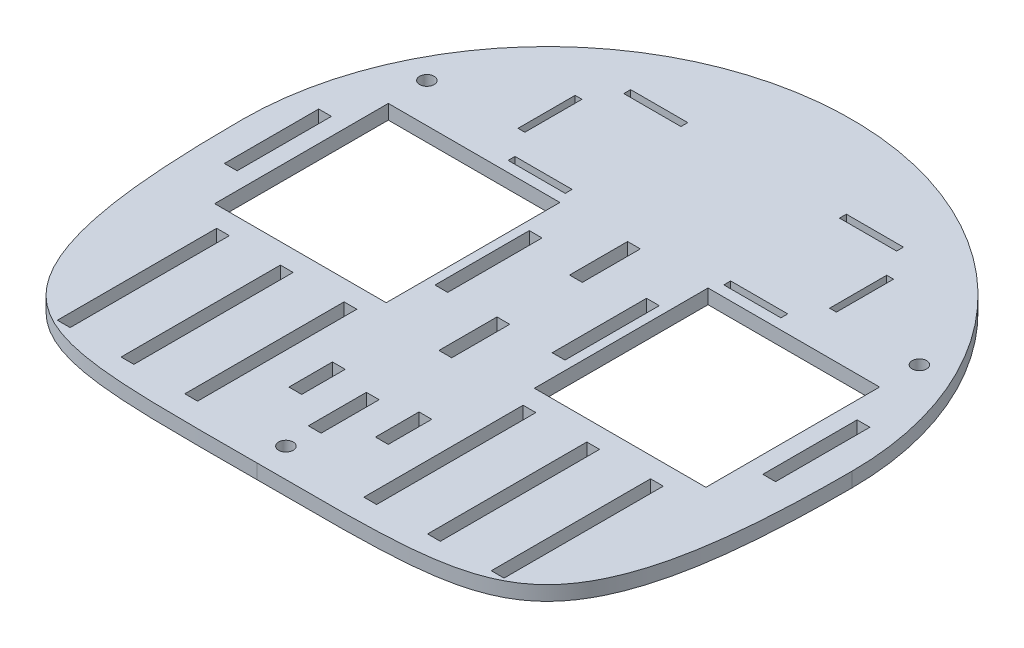
SolidWorks part; units mm, degrees
ref_plane "Front Plane" through (0, 0, 0) normal (0, 0, 1) x (1, 0, 0)
ref_plane "Top Plane" through (0, 0, 0) normal (0, 1, 0) x (1, 0, 0)
ref_plane "Right Plane" through (0, 0, 0) normal (1, 0, 0) x (0, 0, -1)
sketch "Sketch1" plane through (0, 0, 0) normal (0, 1, 0) x (1, 0, 0)
  line L0 (0, 0) -> (-157.9039, -157.9039) construction
  line L1 (0, -127) -> (0, 133.35) construction
  arc A0 (133.35, 0) -> (-133.35, 0) centre (0, 0) ccw
  spline S0 degree 3 poles (-133.35, 0) (-133.35, -51.198) (-123.8034, -129.8051) (-58.428, -127) (0, -127) knots 0 0 0 0 0.502616 1 1 1 1
  spline S1 degree 3 poles (133.35, 0) (133.35, -51.198) (123.8034, -129.8051) (58.428, -127) (0, -127) knots 0 0 0 0 0.502616 1 1 1 1
  dimension "D1" = 266.7
extrude "Base" add sketch "Sketch1" along normal blind 6.35
sketch "ShaftLayout" plane through (0, 6.35, 0) normal (0, 1, 0) x (1, 0, 0)
  line L0 (-133.35, 0) -> (133.35, 0) construction
  line L1 (0, 133.35) -> (0, -127) construction
  line L2 (-113.4353, -6.35) -> (-103.5293, -6.35)
  line L3 (-36.3853, -38) -> (-94.3853, -38)
  line L4 (-36.3853, -38) -> (-36.3853, 38)
  line L5 (-36.3853, 38) -> (-94.3853, 38)
  line L6 (-94.3853, -38) -> (-94.3853, 38)
  line L7 (-36.3853, -38) -> (-94.3853, 38) construction
  line L8 (-36.3853, 38) -> (-94.3853, -38) construction
  line L9 (-100.7353, -15.875) -> (-103.5293, -15.875)
  line L10 (-100.7353, -15.875) -> (-100.7353, 15.875)
  line L11 (-100.7353, 15.875) -> (-103.5293, 15.875)
  line L12 (-103.5293, -15.875) -> (-103.5293, 15.875)
  line L13 (-100.7353, -15.875) -> (-103.5293, 15.875) construction
  line L14 (-100.7353, 15.875) -> (-103.5293, -15.875) construction
  line L15 (-113.4353, -6.35) -> (-113.4353, 6.35)
  line L16 (-103.5293, -6.35) -> (-103.5293, 6.35)
  line L17 (-113.4353, 6.35) -> (-103.5293, 6.35)
  line L18 (-113.4353, -6.35) -> (-103.5293, 6.35) construction
  line L19 (-103.5293, -6.35) -> (-113.4353, 6.35) construction
  line L20 (-115.0228, -9.525) -> (-113.4353, -9.525)
  line L21 (-115.0228, -9.525) -> (-115.0228, 9.525)
  line L22 (-113.4353, -9.525) -> (-113.4353, 9.525)
  line L23 (-115.0228, 9.525) -> (-113.4353, 9.525)
  line L24 (-115.0228, -9.525) -> (-113.4353, 9.525) construction
  line L25 (-113.4353, -9.525) -> (-115.0228, 9.525) construction
  line L26 (-126.1353, -7.9375) -> (-115.0228, -7.9375)
  line L27 (-126.1353, -7.9375) -> (-126.1353, 7.9375)
  line L28 (-115.0228, -7.9375) -> (-115.0228, 7.9375)
  line L29 (-126.1353, 7.9375) -> (-115.0228, 7.9375)
  line L30 (-126.1353, -7.9375) -> (-115.0228, 7.9375) construction
  line L31 (-115.0228, -7.9375) -> (-126.1353, 7.9375) construction
  line L32 (-17.3353, -7.9375) -> (-28.4478, -7.9375)
  line L33 (-30.0353, -9.525) -> (-28.4478, -9.525)
  line L34 (-30.0353, -9.525) -> (-30.0353, 9.525)
  line L35 (-30.0353, 9.525) -> (-28.4478, 9.525)
  line L36 (-28.4478, -9.525) -> (-28.4478, 9.525)
  line L37 (-30.0353, -9.525) -> (-28.4478, 9.525) construction
  line L38 (-30.0353, 9.525) -> (-28.4478, -9.525) construction
  line L39 (-17.3353, -7.9375) -> (-17.3353, 7.9375)
  line L40 (-28.4478, -7.9375) -> (-28.4478, 7.9375)
  line L41 (-17.3353, 7.9375) -> (-28.4478, 7.9375)
  line L42 (-17.3353, -7.9375) -> (-28.4478, 7.9375) construction
  line L43 (-28.4478, -7.9375) -> (-17.3353, 7.9375) construction
  line L45 (-67.3853, -10.033) -> (-56.3853, -10.033)
  line L46 (-67.3853, -10.033) -> (-67.3853, 10.033)
  line L47 (-67.3853, 10.033) -> (-56.3853, 10.033)
  line L48 (-56.3853, -10.033) -> (-56.3853, 10.033)
  line L49 (-67.3853, -10.033) -> (-56.3853, 10.033) construction
  line L50 (-67.3853, 10.033) -> (-56.3853, -10.033) construction
  arc A0 (133.35, 0) -> (-133.35, 0) centre (0, 0) ccw construction
  point P10 (-65.3853, 0)
  point P15 (-102.1323, 0)
  point P20 (-29.2416, 0)
  point P21 (-108.4823, 0)
  point P22 (-114.2291, 0)
  point P23 (-120.5791, 0)
  point P40 (-61.8853, 0)
  point P41 (-22.8916, 0)
  dimension "D1" = 58
  dimension "D2" = 76
  dimension "D3" = 6.35
  dimension "D4" = 2.794
  dimension "D5" = 31.75
  dimension "D6" = 9.906
  dimension "D7" = 12.7
  dimension "D8" = 19.05
  dimension "D9" = 1.5875
  dimension "D10" = 12.7
  dimension "D11" = 15.875
  dimension "D12" = 19.05
  dimension "D13" = 1.5875
  dimension "D14" = 15.875
  dimension "D15" = 12.7
  dimension "D16" = 6.35
  dimension "D17" = 20.066
  dimension "D18" = 20
  dimension "D19" = 11
sketch "MotorLayout" plane through (0, 6.35, 0) normal (0, 1, 0) x (1, 0, 0)
  line L0 (-97.7353, -81.74) -> (-117.7353, -81.74) construction
  line L1 (-97.7353, -110.24) -> (-21.7353, -110.24)
  line L2 (-97.7353, -110.24) -> (-97.7353, -53.24)
  line L3 (-97.7353, -53.24) -> (-21.7353, -53.24)
  line L4 (-21.7353, -110.24) -> (-21.7353, -53.24)
  line L5 (-97.7353, -110.24) -> (-21.7353, -53.24) construction
  line L6 (-97.7353, -53.24) -> (-21.7353, -110.24) construction
  line L7 (-113.4353, -92.0587) -> (-103.5293, -92.0587)
  line L8 (-103.5293, -97.615) -> (-100.7353, -97.615)
  line L9 (-103.5293, -97.615) -> (-103.5293, -65.865)
  line L10 (-103.5293, -65.865) -> (-100.7353, -65.865)
  line L11 (-100.7353, -97.615) -> (-100.7353, -65.865)
  line L12 (-103.5293, -97.615) -> (-100.7353, -65.865) construction
  line L13 (-103.5293, -65.865) -> (-100.7353, -97.615) construction
  line L14 (-36.3853, -38) -> (-94.3853, -38) construction
  line L15 (-113.4353, -92.0587) -> (-113.4353, -71.4212)
  line L16 (-103.5293, -92.0587) -> (-103.5293, -71.4212)
  line L17 (-113.4353, -71.4212) -> (-103.5293, -71.4212)
  line L18 (-113.4353, -92.0587) -> (-103.5293, -71.4212) construction
  line L19 (-103.5293, -92.0587) -> (-113.4353, -71.4212) construction
  line L20 (-102.1323, -1000) -> (-102.1323, 49000) construction
  point P0 (-59.7353, -81.74)
  point P7 (-102.1323, -81.74)
  point P14 (-108.4823, -81.74)
  dimension "D1" = 20
  dimension "D2" = 76
  dimension "D3" = 57
  dimension "D4" = 2.794
  dimension "D5" = 15.24
  dimension "D6" = 31.75
  dimension "D7" = 20.6375
  dimension "D8" = 12.7
  dimension "D9" = 3
sketch "Sketch6" plane through (0, 6.35, 0) normal (0, 1, 0) x (1, 0, 0)
  line L0 (-36.3853, -38) -> (-36.3853, 38) construction
  line L1 (-32.4166, -38) -> (-107.4981, -38)
  line L2 (-32.4166, -38) -> (-32.4166, 38)
  line L3 (-32.4166, 38) -> (-107.4981, 38)
  line L4 (-107.4981, -38) -> (-107.4981, 38)
  line L5 (-28.4478, -9.525) -> (-28.4478, 9.525) construction
  line L6 (-103.5293, -15.875) -> (-103.5293, 15.875) construction
  line L7 (0, 133.35) -> (0, -127) construction
  line L8 (28.4478, 20.6375) -> (22.8598, -20.6375) construction
  line L9 (28.4478, -20.6375) -> (22.8598, 20.6375) construction
  line L10 (115.0228, 20.6375) -> (120.6108, -20.6375) construction
  line L11 (115.0228, -20.6375) -> (120.6108, 20.6375) construction
  line L12 (-133.35, 0) -> (133.35, 0) construction
  line L13 (-115.0228, -20.6375) -> (-120.6108, -20.6375)
  line L14 (-115.0228, -20.6375) -> (-115.0228, 20.6375)
  line L15 (-115.0228, 20.6375) -> (-120.6108, 20.6375)
  line L16 (-120.6108, -20.6375) -> (-120.6108, 20.6375)
  line L17 (-115.0228, -20.6375) -> (-120.6108, 20.6375) construction
  line L18 (-115.0228, 20.6375) -> (-120.6108, -20.6375) construction
  line L19 (-115.0228, -9.525) -> (-115.0228, 9.525) construction
  line L20 (-126.1353, 7.9375) -> (-115.0228, 7.9375) construction
  line L21 (-17.3353, 7.9375) -> (-28.4478, 7.9375) construction
  line L22 (-28.4478, -20.6375) -> (-22.8598, -20.6375)
  line L23 (-28.4478, -20.6375) -> (-28.4478, 20.6375)
  line L24 (-28.4478, 20.6375) -> (-22.8598, 20.6375)
  line L25 (-22.8598, -20.6375) -> (-22.8598, 20.6375)
  line L26 (-28.4478, -20.6375) -> (-22.8598, 20.6375) construction
  line L27 (-28.4478, 20.6375) -> (-22.8598, -20.6375) construction
  line L28 (22.8598, -20.6375) -> (22.8598, 20.6375)
  line L29 (28.4478, 20.6375) -> (22.8598, 20.6375)
  line L30 (28.4478, -20.6375) -> (28.4478, 20.6375)
  line L31 (28.4478, -20.6375) -> (22.8598, -20.6375)
  line L32 (120.6108, -20.6375) -> (120.6108, 20.6375)
  line L33 (115.0228, 20.6375) -> (120.6108, 20.6375)
  line L34 (115.0228, -20.6375) -> (115.0228, 20.6375)
  line L35 (115.0228, -20.6375) -> (120.6108, -20.6375)
  line L36 (107.4981, -38) -> (107.4981, 38)
  line L37 (32.4166, 38) -> (107.4981, 38)
  line L38 (32.4166, -38) -> (32.4166, 38)
  line L39 (32.4166, -38) -> (107.4981, -38)
  point P16 (-117.8168, 0)
  point P27 (-25.6538, 0)
  point P44 (25.6538, 0)
  point P45 (117.8168, 0)
  dimension "D1" = 3.9688
  dimension "D2" = 3.9688
  dimension "D3" = 12.7
  dimension "D4" = 12.7
  dimension "D5" = 5.588
  dimension "D6" = 5.588
extrude "WheelShaftCut" cut sketch "Sketch6" against normal through all
sketch "Sketch8" plane through (0, 6.35, 0) normal (0, 1, 0) x (1, 0, 0)
  line L0 (-97.7353, -81.74) -> (-21.7353, -81.74) construction
  line L1 (-21.7353, -110.24) -> (-21.7353, -53.24) construction
  line L2 (-97.7353, -53.24) -> (-21.7353, -53.24) construction
  line L3 (-36.3805, -116.59) -> (-41.9685, -116.59)
  line L4 (-36.3805, -116.59) -> (-36.3805, -46.89)
  line L5 (-36.3805, -46.89) -> (-41.9685, -46.89)
  line L6 (-41.9685, -116.59) -> (-41.9685, -46.89)
  line L7 (-36.3805, -116.59) -> (-41.9685, -46.89) construction
  line L8 (-36.3805, -46.89) -> (-41.9685, -116.59) construction
  line L9 (-64.2639, -116.59) -> (-69.8519, -116.59)
  line L10 (-64.2639, -116.59) -> (-64.2639, -46.89)
  line L11 (-64.2639, -46.89) -> (-69.8519, -46.89)
  line L12 (-69.8519, -116.59) -> (-69.8519, -46.89)
  line L13 (-64.2639, -116.59) -> (-69.8519, -46.89) construction
  line L14 (-64.2639, -46.89) -> (-69.8519, -116.59) construction
  line L15 (-92.1473, -116.59) -> (-97.7353, -116.59)
  line L16 (-92.1473, -116.59) -> (-92.1473, -46.89)
  line L17 (-92.1473, -46.89) -> (-97.7353, -46.89)
  line L18 (-97.7353, -116.59) -> (-97.7353, -46.89)
  line L19 (-92.1473, -116.59) -> (-97.7353, -46.89) construction
  line L20 (-92.1473, -46.89) -> (-97.7353, -116.59) construction
  line L21 (-97.7353, -110.24) -> (-97.7353, -53.24) construction
  line L22 (0, 133.35) -> (0, -127) construction
  line L23 (21.7353, -72.215) -> (16.1473, -91.265) construction
  line L24 (21.7353, -91.265) -> (16.1473, -72.215) construction
  line L25 (21.7353, -81.74) -> (18.9413, -81.74) construction
  line L26 (92.1473, -46.89) -> (97.7353, -116.59) construction
  line L27 (92.1473, -116.59) -> (97.7353, -46.89) construction
  line L28 (64.2639, -46.89) -> (69.8519, -116.59) construction
  line L29 (64.2639, -116.59) -> (69.8519, -46.89) construction
  line L30 (36.3805, -46.89) -> (41.9685, -116.59) construction
  line L31 (36.3805, -116.59) -> (41.9685, -46.89) construction
  line L32 (97.7353, -81.74) -> (21.7353, -81.74) construction
  line L33 (16.1473, -91.265) -> (16.1473, -72.215)
  line L34 (21.7353, -72.215) -> (16.1473, -72.215)
  line L35 (21.7353, -91.265) -> (21.7353, -72.215)
  line L36 (21.7353, -91.265) -> (16.1473, -91.265)
  line L37 (97.7353, -116.59) -> (97.7353, -46.89)
  line L38 (92.1473, -46.89) -> (97.7353, -46.89)
  line L39 (92.1473, -116.59) -> (92.1473, -46.89)
  line L40 (92.1473, -116.59) -> (97.7353, -116.59)
  line L41 (69.8519, -116.59) -> (69.8519, -46.89)
  line L42 (-21.7353, -81.74) -> (-18.9413, -81.74) construction
  line L43 (64.2639, -46.89) -> (69.8519, -46.89)
  line L44 (-21.7353, -91.265) -> (-16.1473, -91.265)
  line L45 (-21.7353, -91.265) -> (-21.7353, -72.215)
  line L46 (-21.7353, -72.215) -> (-16.1473, -72.215)
  line L47 (-16.1473, -91.265) -> (-16.1473, -72.215)
  line L48 (-21.7353, -91.265) -> (-16.1473, -72.215) construction
  line L49 (-21.7353, -72.215) -> (-16.1473, -91.265) construction
  line L50 (64.2639, -116.59) -> (64.2639, -46.89)
  line L51 (64.2639, -116.59) -> (69.8519, -116.59)
  line L52 (41.9685, -116.59) -> (41.9685, -46.89)
  line L53 (36.3805, -46.89) -> (41.9685, -46.89)
  line L54 (36.3805, -116.59) -> (36.3805, -46.89)
  line L55 (36.3805, -116.59) -> (41.9685, -116.59)
  point P5 (-39.1745, -81.74)
  point P14 (-67.0579, -81.74)
  point P19 (-94.9413, -81.74)
  point P52 (94.9413, -81.74)
  point P53 (67.0579, -81.74)
  point P54 (39.1745, -81.74)
  dimension "D1" = 5.588
  dimension "D2" = 6.35
  dimension "D4" = 5.588
  dimension "D5" = 19.05
  dimension "D3" = 3
extrude "MotorCut" cut sketch "Sketch8" against normal through all
sketch "BatteryLayout" plane through (0, 6.35, 0) normal (0, 1, 0) x (1, 0, 0)
  line L0 (0, 133.35) -> (0, -127) construction
  line L1 (-32.4166, 38) -> (-107.4981, 38) construction
  line L2 (-66.675, 45.62) -> (66.675, 45.62)
  line L3 (-66.675, 45.62) -> (-66.675, 93.245)
  line L4 (-66.675, 93.245) -> (66.675, 93.245)
  line L5 (66.675, 45.62) -> (66.675, 93.245)
  line L6 (-66.675, 45.62) -> (66.675, 93.245) construction
  line L7 (-66.675, 93.245) -> (66.675, 45.62) construction
  arc A0 (133.35, 0) -> (-133.35, 0) centre (0, 0) ccw construction
  point P6 (0, 69.4325)
  dimension "D1" = 133.35
  dimension "D2" = 47.625
  dimension "D3" = 7.62
sketch "Sketch10" plane through (0, 6.35, 0) normal (0, 1, 0) x (1, 0, 0)
  line L0 (-66.675, 93.245) -> (66.675, 93.245) construction
  line L1 (-59.69, 42.62) -> (-34.69, 42.62)
  line L2 (-59.69, 42.62) -> (-59.69, 45.62)
  line L3 (-59.69, 45.62) -> (-34.69, 45.62)
  line L4 (-34.69, 42.62) -> (-34.69, 45.62)
  line L5 (-59.69, 42.62) -> (-34.69, 45.62) construction
  line L6 (-59.69, 45.62) -> (-34.69, 42.62) construction
  line L7 (-59.69, 96.245) -> (-34.69, 96.245)
  line L8 (-59.69, 96.245) -> (-59.69, 93.245)
  line L9 (-59.69, 93.245) -> (-34.69, 93.245)
  line L10 (-34.69, 96.245) -> (-34.69, 93.245)
  line L11 (-59.69, 96.245) -> (-34.69, 93.245) construction
  line L12 (-59.69, 93.245) -> (-34.69, 96.245) construction
  line L13 (-66.675, 45.62) -> (66.675, 45.62) construction
  line L14 (-66.675, 45.62) -> (-66.675, 93.245) construction
  line L15 (0, 69.4325) -> (-66.675, 69.4325) construction
  line L16 (-66.675, 56.9325) -> (-69.675, 56.9325)
  line L17 (-66.675, 56.9325) -> (-66.675, 81.9325)
  line L18 (-66.675, 81.9325) -> (-69.675, 81.9325)
  line L19 (-69.675, 56.9325) -> (-69.675, 81.9325)
  line L20 (0, 133.35) -> (0, -127) construction
  line L21 (59.69, 93.245) -> (34.69, 96.245) construction
  line L22 (59.69, 96.245) -> (34.69, 93.245) construction
  line L23 (59.69, 45.62) -> (34.69, 42.62) construction
  line L24 (59.69, 42.62) -> (34.69, 45.62) construction
  line L25 (69.675, 56.9325) -> (69.675, 81.9325)
  line L26 (66.675, 81.9325) -> (69.675, 81.9325)
  line L27 (66.675, 56.9325) -> (66.675, 81.9325)
  line L28 (66.675, 56.9325) -> (69.675, 56.9325)
  line L29 (34.69, 96.245) -> (34.69, 93.245)
  line L30 (59.69, 93.245) -> (34.69, 93.245)
  line L31 (59.69, 96.245) -> (59.69, 93.245)
  line L32 (59.69, 96.245) -> (34.69, 96.245)
  line L33 (34.69, 42.62) -> (34.69, 45.62)
  line L34 (59.69, 45.62) -> (34.69, 45.62)
  line L35 (59.69, 42.62) -> (59.69, 45.62)
  line L36 (59.69, 42.62) -> (34.69, 42.62)
  point P0 (-47.19, 44.12)
  point P5 (-47.19, 94.745)
  point P20 (-66.675, 69.4325)
  point P40 (66.675, 69.4325)
  point P41 (47.19, 94.745)
  point P42 (47.19, 44.12)
  dimension "D1" = 3
  dimension "D2" = 3
  dimension "D3" = 25
  dimension "D4" = 25
  dimension "D5" = 6.985
  dimension "D6" = 6.985
  dimension "D7" = 3
  dimension "D8" = 25
extrude "VelcroCut" cut sketch "Sketch10" against normal through all
sketch "Sketch11" plane through (0, 6.35, 0) normal (0, 1, 0) x (1, 0, 0)
  line L0 (0, 133.35) -> (0, -127) construction
  line L1 (-133.35, 0) -> (133.35, 0) construction
  line L3 (-34.69, 45.62) -> (-59.69, 45.62) construction
  line L4 (-69.675, 81.9325) -> (-69.675, 56.9325) construction
  arc A0 (133.35, 0) -> (-133.35, 0) centre (0, 0) ccw construction
  circle A1 centre (0, -114.3) radius 3.175
  circle A2 centre (-107.775, 55.145) radius 3.175
  circle A3 centre (107.775, 55.145) radius 3.175
  dimension "D1" = 6.35
  dimension "D2" = 12.7
  dimension "D3" = 6.35
  dimension "D4" = 9.525
  dimension "D5" = 38.1
extrude "ScrewCut" cut sketch "Sketch11" against normal through all
sketch "Sketch13" plane through (0, 6.35, 0) normal (0, 1, 0) x (1, 0, 0)
  line L0 (0, 133.35) -> (0, -127) construction
  line L1 (-2.794, 12.6) -> (2.794, 12.6)
  line L2 (-2.794, 12.6) -> (-2.794, 38)
  line L3 (-2.794, 38) -> (2.794, 38)
  line L4 (2.794, 12.6) -> (2.794, 38)
  line L5 (-2.794, 12.6) -> (2.794, 38) construction
  line L6 (-2.794, 38) -> (2.794, 12.6) construction
  line L7 (107.4981, 38) -> (32.4166, 38) construction
  line L8 (-2.794, -44.55) -> (2.794, -44.55)
  line L9 (-2.794, -44.55) -> (-2.794, -19.15)
  line L10 (-2.794, -19.15) -> (2.794, -19.15)
  line L11 (2.794, -44.55) -> (2.794, -19.15)
  line L12 (-2.794, -44.55) -> (2.794, -19.15) construction
  line L13 (-2.794, -19.15) -> (2.794, -44.55) construction
  line L14 (-2.794, -101.7) -> (2.794, -101.7)
  line L15 (-2.794, -101.7) -> (-2.794, -76.3)
  line L16 (-2.794, -76.3) -> (2.794, -76.3)
  line L17 (2.794, -101.7) -> (2.794, -76.3)
  line L18 (-2.794, -101.7) -> (2.794, -76.3) construction
  line L19 (-2.794, -76.3) -> (2.794, -101.7) construction
  point P0 (0, 25.3)
  point P10 (0, -31.85)
  point P15 (0, -89)
  dimension "D1" = 5.588
  dimension "D2" = 25.4
  dimension "D3" = 0
  dimension "D4" = 3
extrude "SupportStrutCut" cut sketch "Sketch13" against normal through all
